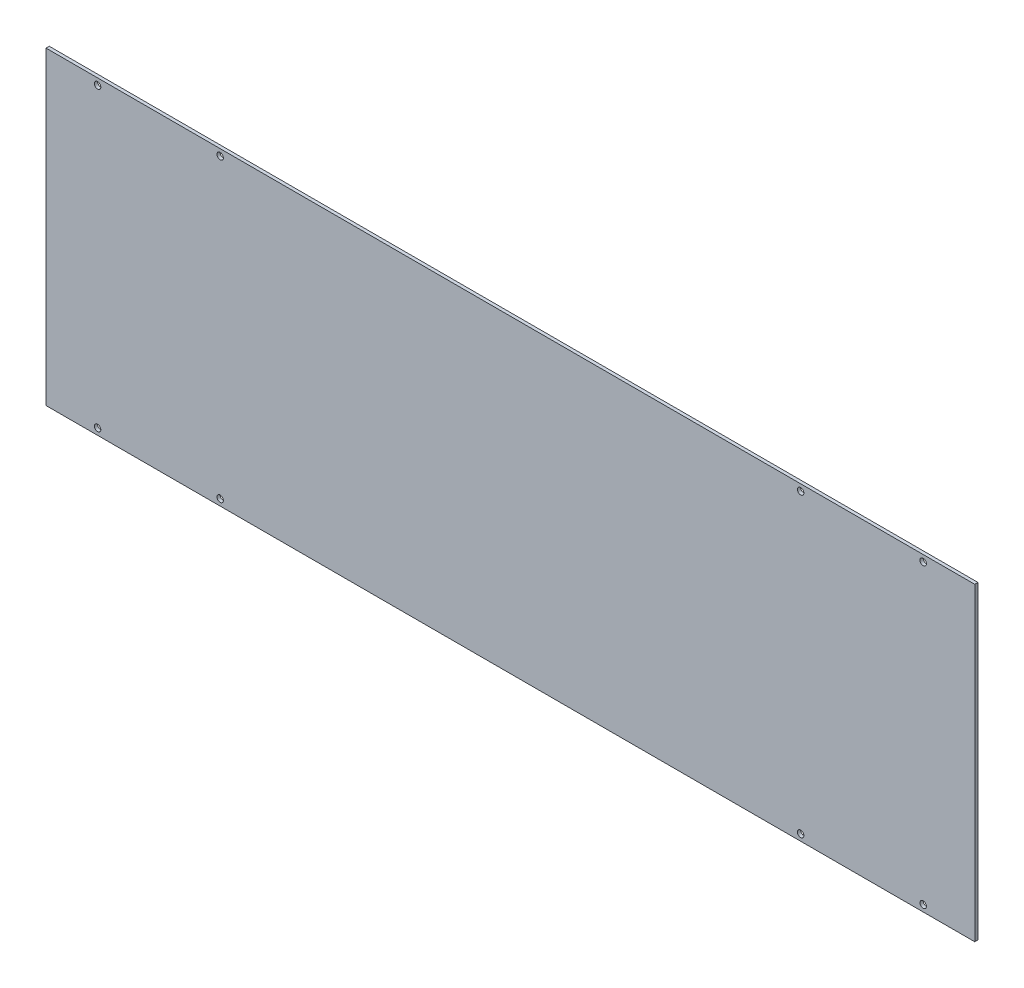
SolidWorks part; units mm, degrees
ref_plane "Front Plane" through (0, 0, 0) normal (0, 0, 1) x (1, 0, 0)
ref_plane "Top Plane" through (0, 0, 0) normal (0, 1, 0) x (1, 0, 0)
ref_plane "Right Plane" through (0, 0, 0) normal (1, 0, 0) x (0, 0, -1)
sketch "Sketch1" plane through (0, 0, 0) normal (0, 0, 1) x (1, 0, 0)
  line L1 (-457.2, -152.4) -> (457.2, -152.4)
  line L2 (-457.2, -152.4) -> (-457.2, 152.4)
  line L3 (-457.2, 152.4) -> (457.2, 152.4)
  line L4 (457.2, -152.4) -> (457.2, 152.4)
  line L5 (-457.2, -152.4) -> (457.2, 152.4) construction
  line L6 (-457.2, 152.4) -> (457.2, -152.4) construction
  point P0 (0, 0)
  dimension "D1" = 914.4
  dimension "D2" = 304.8
extrude "Boss-Extrude1" add sketch "Sketch1" along normal blind 3.175
hole_wizard "1/4 (0.25) Diameter Hole1" positions "Sketch2" profile "Sketch3" hole size "1/4" standard "ANSI Inch" end condition through all
sketch "Sketch2" plane through (0, 0, 3.175) normal (0, 0, 1) x (1, 0, 0)
  line L0 (457.2, 152.4) -> (-457.2, 152.4) construction
  line L1 (-457.2, -152.4) -> (457.2, -152.4) construction
  line L2 (457.2, -152.4) -> (457.2, 152.4) construction
  point P0 (285.75, 146.05)
  point P2 (406.4, 146.05)
  point P4 (406.4, -146.05)
  point P6 (285.75, -146.05)
  dimension "D1" = 6.35
  dimension "D2" = 6.35
  dimension "D3" = 50.8
  dimension "D4" = 171.45
sketch "Sketch3" plane through (285.75, 146.05, 3.175) normal (1, 0, 0) x (0, -1, 0)
  line L0 (0, 0) -> (0, 3.175)
  line L1 (0, 3.175) -> (3.175, 3.175)
  line L2 (3.175, 3.175) -> (3.175, 0)
  line L5 (3.175, 0) -> (0, 0)
  line L11 (0, -6.35) -> (0, 107.95) construction
  dimension "Thru Hole Dia." = 6.35
  dimension "Thru Hole Depth" = 3.175
mirror "Mirror1" about plane through (0, 0, 0) normal (1, 0, 0) of "1/4 (0.25) Diameter Hole1"
